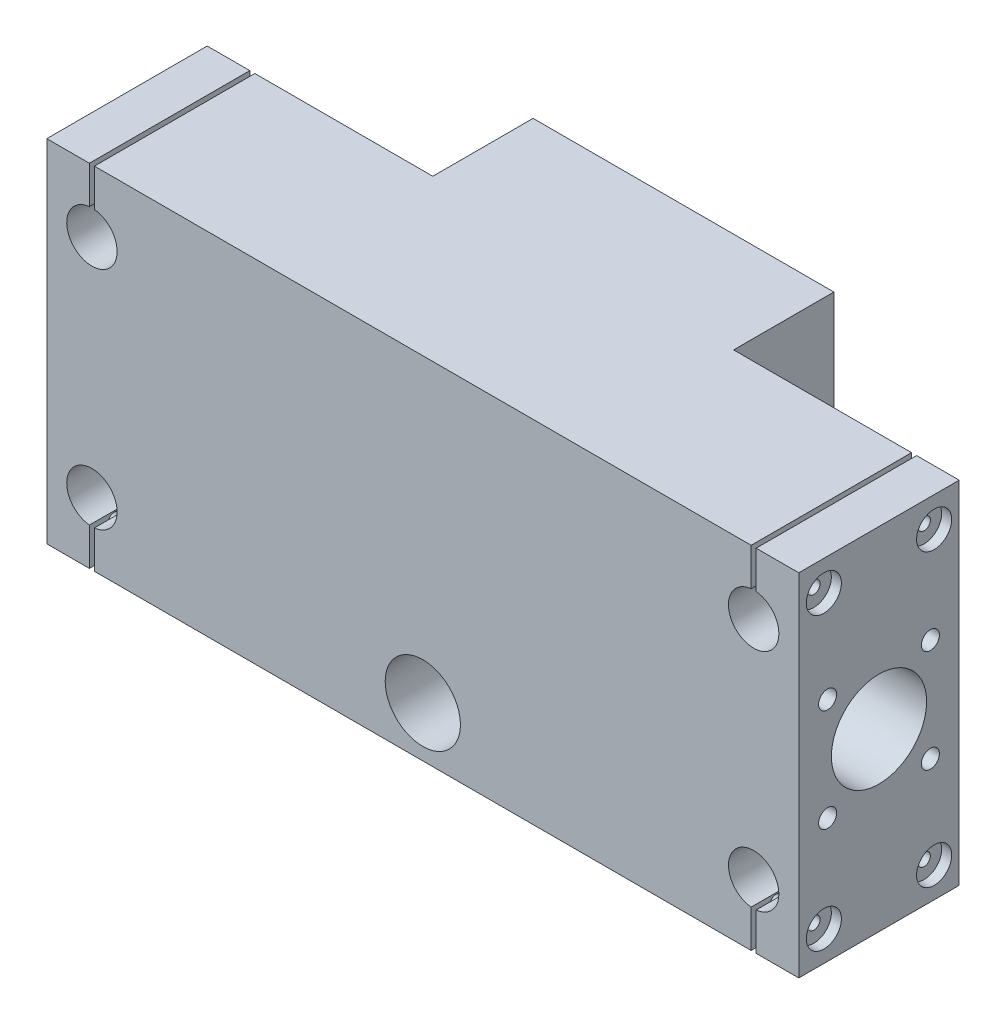
SolidWorks part; units mm, degrees
material "1060 Alloy"
ref_plane "Front Plane" through (0, 0, 0) normal (0, 0, 1) x (1, 0, 0)
ref_plane "Top Plane" through (0, 0, 0) normal (0, 1, 0) x (1, 0, 0)
ref_plane "Right Plane" through (0, 0, 0) normal (1, 0, 0) x (0, 0, -1)
sketch "Sketch1" plane through (0, 0, 0) normal (0, 0, 1) x (1, 0, 0)
  line L1 (-150, 0) -> (0, 0)
  line L2 (-150, 0) -> (-150, -70)
  line L3 (-150, -70) -> (0, -70)
  line L4 (0, 0) -> (0, -70)
  dimension "D1" = 150
  dimension "D2" = 70
extrude "Boss-Extrude1" add sketch "Sketch1" along normal blind 32
sketch "Sketch2" plane through (-150, 0, 0) normal (-1, 0, 0) x (0, 0, 1)
  line L0 (16, 0) -> (16, -70) construction
  line L1 (32, 0) -> (0, 0) construction
  line L2 (32, -70) -> (0, -70) construction
  line L3 (0, -35) -> (32, -35) construction
  line L4 (0, 0) -> (0, -70) construction
  line L5 (32, 0) -> (32, -70) construction
  circle A0 centre (16, -35) radius 9.5
  dimension "D1" = 19
extrude "Linear_bearing-cut-1" cut sketch "Sketch2" against normal blind 55
sketch "Sketch5" plane through (0, 0, 32) normal (0, 0, 1) x (1, 0, 0)
  line L0 (-75, 0) -> (-75, -70) construction
  line L1 (0, 0) -> (-150, 0) construction
  line L2 (-150, -70) -> (0, -70) construction
  line L3 (0, -35) -> (-150, -35) construction
  line L4 (0, -70) -> (0, 0) construction
  line L5 (-150, 0) -> (-150, -70) construction
  line L6 (-141, 0) -> (-141, -12.5) construction
  line L7 (-141, -12.5) -> (-9, -12.5) construction
  line L8 (-9, -12.5) -> (-9, 0) construction
  line L9 (-9, -57.5) -> (-9, -70) construction
  line L10 (-141, -57.5) -> (-9, -57.5) construction
  line L11 (-141, -70) -> (-141, -57.5) construction
  line L12 (-141.5, 0) -> (-141.5, -7.5)
  line L13 (-140.5, 0) -> (-140.5, -7.5)
  line L14 (-8.5, 0) -> (-8.5, -7.5)
  line L15 (-9.5, 0) -> (-9.5, -7.5)
  line L16 (-141.5, -70) -> (-141.5, -62.5)
  line L17 (-140.5, -70) -> (-140.5, -62.5)
  line L18 (-9.5, -70) -> (-9.5, -62.5)
  line L19 (-8.5, -70) -> (-8.5, -62.5)
  line L20 (-141.5, 0) -> (-140.5, 0)
  line L21 (-9.5, 0) -> (-8.5, 0)
  line L22 (-9.5, -70) -> (-8.5, -70)
  line L23 (-141.5, -70) -> (-140.5, -70)
  arc A0 (-141.5, -7.5) -> (-140.5, -7.5) centre (-141, -12.5) ccw
  arc A1 (-8.5, -7.5) -> (-9.5, -7.5) centre (-9, -12.5) cw
  arc A2 (-141.5, -62.5) -> (-140.5, -62.5) centre (-141, -57.5) cw
  arc A3 (-8.5, -62.5) -> (-9.5, -62.5) centre (-9, -57.5) ccw
  dimension "D1" = 9
  dimension "D3" = 12.5
  dimension "D5" = 0.5
  dimension "D6" = 7.5
extrude "Y-axis-shafts-cut" cut sketch "Sketch5" against normal through all
sketch "Sketch6" plane through (-95, 0, 0) normal (-1, 0, 0) x (0, 0, 1)
  line L0 (16, -25.5) -> (16, -44.5) construction
  circle A0 centre (16, -35) radius 9.5 construction
  circle A1 centre (16, -35) radius 9.5 construction
  circle A2 centre (16, -35) radius 6
  dimension "D1" = 12
sketch "Sketch7" plane through (0, 0, 0) normal (1, 0, 0) x (0, 0, -1)
  circle A0 centre (-16, -35) radius 9.5
  dimension "D1" = 19
extrude "Linear-bearing-cut-2" cut sketch "Sketch7" against normal blind 55
extrude "between-bearings" cut sketch "Sketch6" against normal through all
sketch "Sketch8" plane through (-150, 0, 0) normal (-1, 0, 0) x (0, 0, 1)
  line L0 (5, 0) -> (5, -6) construction
  line L1 (32, 0) -> (0, 0) construction
  line L2 (5, -6) -> (27, -6) construction
  line L3 (27, -6) -> (27, 0) construction
  line L4 (0, 0) -> (0, -70) construction
  line L5 (32, 0) -> (32, -70) construction
  line L6 (16, 0) -> (16, -70) construction
  line L7 (32, -70) -> (0, -70) construction
  line L8 (0, -35) -> (32, -35) construction
  line L9 (5, -39.9148) -> (4.7174, -39.9148) construction
  circle A0 centre (5, -6) radius 3.5
  circle A1 centre (27, -6) radius 3.5
  circle A2 centre (27, -64) radius 3.5
  circle A3 centre (5, -64) radius 3.5
  dimension "D4" = 7
  dimension "D1" = 5
  dimension "D3" = 6
extrude "shaft-holder-screw-cut" cut sketch "Sketch8" against normal blind 4
sketch "Sketch9" plane through (-146, 0, 0) normal (-1, 0, 0) x (0, 0, 1)
  line L0 (5, -2.5) -> (5, -9.5) construction
  line L1 (27, -2.5) -> (27, -9.5) construction
  line L2 (27, -60.5) -> (27, -67.5) construction
  line L3 (5, -60.5) -> (5, -67.5) construction
  circle A0 centre (5, -6) radius 3.5 construction
  circle A1 centre (5, -6) radius 3.5 construction
  circle A2 centre (27, -6) radius 3.5 construction
  circle A3 centre (27, -6) radius 3.5 construction
  circle A4 centre (27, -64) radius 3.5 construction
  circle A5 centre (27, -64) radius 3.5 construction
  circle A6 centre (5, -64) radius 3.5 construction
  circle A7 centre (5, -64) radius 3.5 construction
  circle A8 centre (5, -6) radius 1.25
  circle A9 centre (27, -6) radius 1.25
  circle A10 centre (5, -64) radius 1.25
  circle A11 centre (27, -64) radius 1.25
  dimension "D1" = 2.5
extrude "shaft-holder-screw-cut2" cut sketch "Sketch9" against normal blind 20
sketch "Sketch10" plane through (0, 0, 0) normal (1, 0, 0) x (0, 0, -1)
  line L0 (-27, 0) -> (-27, -6) construction
  line L1 (-32, 0) -> (0, 0) construction
  line L2 (-27, -6) -> (-5, -6) construction
  line L3 (-5, -6) -> (-5, 0) construction
  line L4 (-32, -70) -> (-32, 0) construction
  line L5 (0, -70) -> (0, 0) construction
  line L6 (-16, 0) -> (-16, -70) construction
  line L7 (-32, -70) -> (0, -70) construction
  line L8 (-32, -35) -> (0, -35) construction
  circle A0 centre (-27, -6) radius 3.5
  circle A1 centre (-5, -6) radius 3.5
  circle A2 centre (-5, -64) radius 3.5
  circle A3 centre (-27, -64) radius 3.5
  dimension "D4" = 7
  dimension "D1" = 5
  dimension "D2" = 6
extrude "shaft-holder-screw-cut-3" cut sketch "Sketch10" against normal blind 2
sketch "Sketch11" plane through (-2, 0, 0) normal (1, 0, 0) x (0, 0, -1)
  line L0 (-27, -2.5) -> (-27, -9.5) construction
  line L1 (-5, -2.5) -> (-5, -9.5) construction
  line L2 (-5, -60.5) -> (-5, -67.5) construction
  line L3 (-27, -60.5) -> (-27, -67.5) construction
  circle A0 centre (-27, -6) radius 3.5 construction
  circle A1 centre (-27, -6) radius 3.5 construction
  circle A2 centre (-5, -6) radius 3.5 construction
  circle A3 centre (-5, -6) radius 3.5 construction
  circle A4 centre (-5, -64) radius 3.5 construction
  circle A5 centre (-5, -64) radius 3.5 construction
  circle A6 centre (-27, -64) radius 3.5 construction
  circle A7 centre (-27, -64) radius 3.5 construction
  circle A8 centre (-27, -6) radius 1.25
  circle A9 centre (-5, -6) radius 1.25
  circle A10 centre (-5, -64) radius 1.25
  circle A11 centre (-27, -64) radius 1.25
  dimension "D1" = 2.5
extrude "shaft-holder-screw-cut-4" cut sketch "Sketch11" against normal blind 20
sketch "Sketch12" plane through (0, 0, 0) normal (1, 0, 0) x (0, 0, -1)
  line L0 (-5.75, 0) -> (-5.75, -24.75) construction
  line L1 (-32, 0) -> (0, 0) construction
  line L2 (-5.75, -24.75) -> (0, -24.75) construction
  line L3 (0, -70) -> (0, 0) construction
  line L4 (-16, 0) -> (-16, -70) construction
  line L5 (-32, -70) -> (0, -70) construction
  line L6 (0, -35) -> (-32, -35) construction
  line L7 (-32, -70) -> (-32, 0) construction
  circle A0 centre (-5.75, -24.75) radius 1.8
  circle A1 centre (-26.25, -24.75) radius 1.8
  circle A2 centre (-5.75, -45.25) radius 1.8
  circle A3 centre (-26.25, -45.25) radius 1.8
  dimension "D3" = 3.6
  dimension "D1" = 5.75
  dimension "D2" = 24.75
extrude "Linear-bearing-srew1" cut sketch "Sketch12" against normal blind 14
sketch "Sketch13" plane through (-150, 0, 0) normal (-1, 0, 0) x (0, 0, 1)
  line L0 (27.5, 0) -> (27.5, -24.75) construction
  line L1 (32, 0) -> (0, 0) construction
  line L2 (27.5, -24.75) -> (32, -24.75) construction
  line L3 (32, 0) -> (32, -70) construction
  line L4 (16, 0) -> (16, -70) construction
  line L5 (32, -70) -> (0, -70) construction
  line L6 (32, -35) -> (0, -35) construction
  line L7 (0, 0) -> (0, -70) construction
  circle A0 centre (27.5, -24.75) radius 1.85
  circle A1 centre (4.5, -24.75) radius 1.85
  circle A2 centre (27.5, -45.25) radius 1.85
  circle A3 centre (4.5, -45.25) radius 1.85
  dimension "D3" = 3.7
  dimension "D1" = 24.75
  dimension "D2" = 4.5
extrude "Linear-bearing-screw2" cut sketch "Sketch13" against normal blind 14
sketch "Sketch14" plane through (0, 0, 0) normal (0, 0, -1) x (-1, 0, 0)
  line L0 (140.5, -70) -> (9.5, -70) construction
  line L1 (0, -70) -> (0, 0) construction
  circle A0 centre (75, -60) radius 7.5
  dimension "D3" = 15
  dimension "D1" = 10
  dimension "D2" = 75
extrude "Cut-Extrude1" cut sketch "Sketch14" against normal through all
sketch "Sketch15" plane through (0, 0, 0) normal (0, 0, -1) x (-1, 0, 0)
  line L0 (9.5, 0) -> (140.5, 0) construction
  line L1 (45, 0) -> (105, 0)
  line L2 (45, 0) -> (45, -38)
  line L3 (45, -38) -> (105, -38)
  line L4 (105, 0) -> (105, -38)
  line L5 (75, -70) -> (75, 0) construction
  line L6 (140.5, -70) -> (9.5, -70) construction
  point P10 (75, 0)
  dimension "D1" = 38
  dimension "D2" = 60
extrude "Boss-Extrude2" add sketch "Sketch15" along normal blind 20
